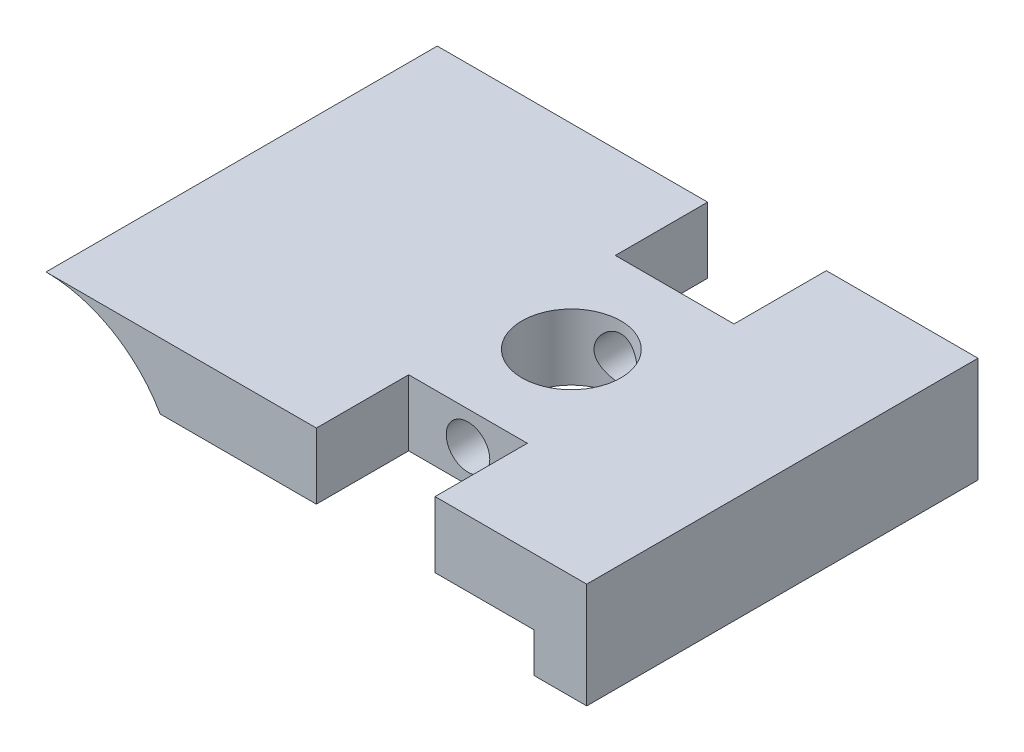
SolidWorks part; units mm, degrees
ref_plane "Front Plane" through (0, 0, 0) normal (0, 0, 1) x (1, 0, 0)
ref_plane "Top Plane" through (0, 0, 0) normal (0, 1, 0) x (1, 0, 0)
ref_plane "Right Plane" through (0, 0, 0) normal (1, 0, 0) x (0, 0, -1)
sketch "Sketch3" plane through (0, 0, 0) normal (0, 0, 1) x (1, 0, 0)
  line L0 (-20.5, 2.5) -> (-11.8397, -2.5) construction
  line L1 (-11.8397, -2.5) -> (20.5, -2.5)
  line L3 (-20.5, 2.5) -> (20.5, 2.5)
  line L4 (20.5, -2.5) -> (20.5, 2.5)
  line L5 (-13.35, -1.628) -> (20.5, 2.5) construction
  line L6 (-20.5, 2.5) -> (20.5, -2.5) construction
  arc A0 (-20.5, 2.5) -> (-11.8397, -2.5) centre (-20.5, -7.5) cw
  point P0 (0, 0)
  point P6 (0, 2.5)
  dimension "D3" = 10
  dimension "D1" = 41
  dimension "D2" = 150
  dimension "D4" = 5
extrude "Boss-Extrude1" add sketch "Sketch3" along normal mid plane 29.67
sketch "Sketch4" plane through (0, 0, 14.835) normal (0, 0, 1) x (1, 0, 0)
  line L0 (20.5, -2.5) -> (20.5, 2.5) construction
  line L1 (20.5, 2.5) -> (-20.5, 2.5) construction
  line L2 (9, -2.5) -> (0, -2.5)
  line L3 (9, -2.5) -> (9, 2.5)
  line L4 (9, 2.5) -> (0, 2.5)
  line L5 (0, -2.5) -> (0, 2.5)
  line L6 (9, -2.5) -> (0, 2.5) construction
  line L7 (9, 2.5) -> (0, -2.5) construction
  circle A2 centre (4.5, 0) radius 1.65
  point P0 (20.5, 0)
  dimension "D1" = 3.3
  dimension "D5" = 16
extrude "Cut-Extrude1" cut sketch "Sketch4" against normal up to next contours A2 region at (4.5, 0, 14.835)
extrude "Cut-Extrude3" cut sketch "Sketch4<3>" against normal blind 7
sketch "Sketch4<3>" plane through (0, 0, 14.835) normal (0, 0, 1) x (1, 0, 0) same geometry as "Sketch4"
mirror "Mirror1" about plane through (0, 0, 0) normal (0, 0, 1) of "Cut-Extrude3"
sketch "Sketch5" plane through (0, 2.5, 0) normal (0, 1, 0) x (1, 0, 0)
  line L0 (20.5, -14.835) -> (20.5, 14.835) construction
  circle A0 centre (4.5, 0) radius 3.75
  point P7 (20.5, 0)
  dimension "D2" = 7.5
  dimension "D1" = 16
extrude "Cut-Extrude2" cut sketch "Sketch5" against normal up to next
sketch "Sketch6" plane through (0, 0, 14.835) normal (0, 0, 1) x (1, 0, 0)
  line L0 (20.5, -2.5) -> (20.5, -5.5)
  line L1 (20.5, -5.5) -> (16.5, -5.5)
  line L2 (16.5, -5.5) -> (16.5, -2.5)
  line L3 (9, -2.5) -> (20.5, -2.5) construction
  line L4 (16.5, -2.5) -> (20.5, -2.5)
  dimension "D1" = 3
  dimension "D2" = 4
extrude "Boss-Extrude2" add sketch "Sketch6" against normal up to surface (29.67 mm away) up to face at (14.75, 0, -14.835)
